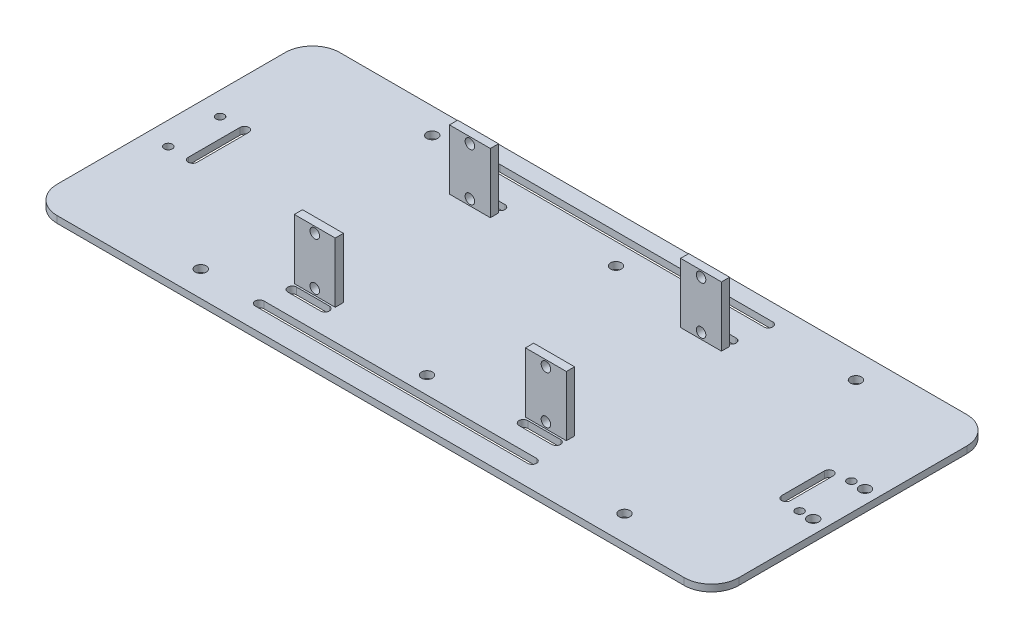
SolidWorks part; units mm, degrees
note: The reader was unsure of these and kept them because the rebuilt part matched: shared geometry of "草图1<3>".
ref_plane "前视基准面" through (0, 0, 0) normal (0, 0, 1) x (1, 0, 0)
ref_plane "上视基准面" through (0, 0, 0) normal (0, 1, 0) x (1, 0, 0)
ref_plane "右视基准面" through (0, 0, 0) normal (1, 0, 0) x (0, 0, -1)
other "Configuration Table"
sketch "草图1" plane through (0, 0, 0) normal (0, 1, 0) x (1, 0, 0)
  line L0 (3.7781, 0) -> (167.7978, 0) construction
  line L1 (0, 52.1835) -> (0, -52.1835) construction
  line L2 (115, -51.8188) -> (-115, -51.8188)
  line L3 (125, -41.8188) -> (125, 41.8188)
  line L4 (115, 51.8188) -> (-115, 51.8188)
  line L5 (-125, -41.8188) -> (-125, 41.8188)
  line L6 (125, -51.8188) -> (-125, 51.8188) construction
  line L7 (125, 51.8188) -> (-125, -51.8188) construction
  line L8 (-48.4, 32.2188) -> (-36.4, 32.2188) construction
  line L9 (-48.4, 33.8188) -> (-36.4, 33.8188)
  line L10 (-48.4, 30.6188) -> (-36.4, 30.6188)
  line L11 (-48.4, -32.2188) -> (-36.4, -32.2188) construction
  line L12 (-48.4, -33.8188) -> (-36.4, -33.8188)
  line L13 (-48.4, -30.6188) -> (-36.4, -30.6188)
  line L14 (48.4, -32.2188) -> (36.4, -32.2188) construction
  line L15 (48.4, -33.8188) -> (36.4, -33.8188)
  line L16 (48.4, -30.6188) -> (36.4, -30.6188)
  line L17 (48.4, 32.2188) -> (36.4, 32.2188) construction
  line L18 (48.4, 33.8188) -> (36.4, 33.8188)
  line L19 (48.4, 30.6188) -> (36.4, 30.6188)
  line L20 (108.4, 7.8731) -> (108.4, -7.8731) construction
  line L23 (-50, -42.6194) -> (50, -42.6194) construction
  line L24 (-98.458, 25) -> (-38.458, 25)
  line L25 (-98.458, 25) -> (-98.458, -25)
  line L26 (-98.458, -25) -> (-38.458, -25)
  line L27 (-38.458, 25) -> (-38.458, -25)
  line L28 (7.2728, 26.5) -> (90.2728, 26.5)
  line L29 (7.2728, 26.5) -> (7.2728, -26.5)
  line L30 (7.2728, -26.5) -> (90.2728, -26.5)
  line L31 (90.2728, 26.5) -> (90.2728, -26.5)
  line L32 (-35.1953, 23.2707) -> (1.4972, 23.2707)
  line L33 (-35.1953, 23.2707) -> (-35.1953, -23.2707)
  line L34 (-35.1953, -23.2707) -> (1.4972, -23.2707)
  line L35 (1.4972, 23.2707) -> (1.4972, -23.2707)
  line L40 (-50, -41.0194) -> (50, -41.0194)
  line L41 (-50, -44.2194) -> (50, -44.2194)
  line L42 (-107.902, 9.7565) -> (-107.902, -9.2435) construction
  line L45 (-50, 44.0491) -> (50, 44.0491) construction
  line L46 (-50, 42.4491) -> (50, 42.4491)
  line L47 (-50, 45.6491) -> (50, 45.6491)
  line L50 (110, 7.8731) -> (110, -7.8731)
  line L51 (106.8, 7.8731) -> (106.8, -7.8731)
  line L52 (-106.302, 9.7565) -> (-106.302, -9.2435)
  line L53 (-109.502, 9.7565) -> (-109.502, -9.2435)
  arc A0 (125, 41.8188) -> (115, 51.8188) centre (115, 41.8188) ccw
  arc A1 (115, -51.8188) -> (125, -41.8188) centre (115, -41.8188) ccw
  arc A2 (-115, -51.8188) -> (-125, -41.8188) centre (-115, -41.8188) cw
  arc A3 (-115, 51.8188) -> (-125, 41.8188) centre (-115, 41.8188) ccw
  circle A4 centre (120, 9.5) radius 2
  circle A5 centre (120, -9.5) radius 2
  arc A8 (-48.4, 33.8188) -> (-48.4, 30.6188) centre (-48.4, 32.2188) ccw
  arc A9 (-36.4, 30.6188) -> (-36.4, 33.8188) centre (-36.4, 32.2188) ccw
  arc A10 (-48.4, -33.8188) -> (-48.4, -30.6188) centre (-48.4, -32.2188) cw
  arc A11 (-36.4, -30.6188) -> (-36.4, -33.8188) centre (-36.4, -32.2188) cw
  arc A12 (48.4, -33.8188) -> (48.4, -30.6188) centre (48.4, -32.2188) ccw
  arc A13 (36.4, -30.6188) -> (36.4, -33.8188) centre (36.4, -32.2188) ccw
  arc A14 (48.4, 33.8188) -> (48.4, 30.6188) centre (48.4, 32.2188) cw
  arc A15 (36.4, 30.6188) -> (36.4, 33.8188) centre (36.4, 32.2188) cw
  arc A24 (-50, -41.0194) -> (-50, -44.2194) centre (-50, -42.6194) ccw
  arc A25 (50, -44.2194) -> (50, -41.0194) centre (50, -42.6194) ccw
  arc A28 (-50, 42.4491) -> (-50, 45.6491) centre (-50, 44.0491) cw
  arc A29 (50, 45.6491) -> (50, 42.4491) centre (50, 44.0491) cw
  arc A32 (110, 7.8731) -> (106.8, 7.8731) centre (108.4, 7.8731) ccw
  arc A33 (106.8, -7.8731) -> (110, -7.8731) centre (108.4, -7.8731) ccw
  circle A34 centre (115, 9.5) radius 1.5
  circle A35 centre (115, -9.5) radius 1.5
  circle A36 centre (-116.5676, 9.5) radius 1.5
  circle A37 centre (-116.5676, -9.5) radius 1.5
  arc A38 (-106.302, 9.7565) -> (-109.502, 9.7565) centre (-107.902, 9.7565) ccw
  arc A39 (-109.502, -9.2435) -> (-106.302, -9.2435) centre (-107.902, -9.2435) ccw
  circle A40 centre (-71.7179, 42.4491) radius 2
  circle A41 centre (3.4711, 34.6651) radius 2
  circle A42 centre (83.7149, 42.4491) radius 2
  circle A43 centre (83.7149, -42.4491) radius 2
  circle A44 centre (3.4711, -34.6651) radius 2
  circle A45 centre (-71.7179, -42.4491) radius 2
  point P1 (0, 0)
  point P32 (-42.4, 32.2188)
  point P39 (-42.4, -32.2188)
  point P46 (42.4, -32.2188)
  point P53 (42.4, 32.2188)
  point P60 (0, -42.6194)
  point P65 (-107.902, 0.2565)
  point P69 (-66.1502, 0)
  point P85 (108.4, 0)
  point P96 (-50, 32.2188)
  point P100 (0, 44.0491)
  point P116 (0, 0)
  dimension "D1" = 10
  dimension "D3" = 60
  dimension "D8" = 4
  dimension "D9" = 19
  dimension "D12" = 12
  dimension "D14" = 100
  dimension "D19" = 15
  dimension "D18" = 5
  dimension "D21" = 19
  dimension "D22" = 3
  dimension "D23" = 3
  dimension "D26" = 4
  dimension "D27" = 4
  dimension "D28" = 4
  dimension "D2" = 250
  dimension "D4" = 50
  dimension "D5" = 83
  dimension "D6" = 53
  dimension "D7" = 36.6924
  dimension "D10" = 3.2
  dimension "D11" = 18
  dimension "D13" = 75
  dimension "D15" = 3.2
  dimension "D16" = 19
  dimension "D17" = 5
  dimension "D20" = 3.2
  dimension "D24" = 19
  dimension "D25" = 3.2
extrude "凸台-拉伸1" add sketch "草图1" along normal mid plane 2.5 contours L4 A3 L5 A2 L2 A1 L3 A0 A44 A35 A34 A33 L51 A32 L50 A25 L41 A24 L40 A13 L16 A12 L15 A9 L10 A8 L9 L24 L27 L26 L25 L28 L31 L30 L29 L32 L35 L34 L33 A4 | L27 L24 L25 L26 | L35 L32 L33 L34 | L31 L28 L29 L30
extrude "凸台-拉伸2" add sketch "草图1<3>" along normal mid plane 2.5 contours L31 L28 L29 L30
sketch "草图1<3>" plane through (0, 0, 0) normal (0, 1, 0) x (1, 0, 0) same geometry as "草图1"
sketch "草图3" plane through (0, 1.25, 0) normal (0, 1, 0) x (1, 0, 0)
  line L0 (0, 0) -> (-129.9126, 0) construction
  line L1 (0, 0) -> (0, 63.0032) construction
  line L2 (-49.8914, -26.9486) -> (-34.8914, -26.9486)
  line L3 (-49.8914, 29.9486) -> (-34.8914, 29.9486)
  line L4 (-49.8914, 29.9486) -> (-49.8914, 26.9486)
  line L5 (-49.8914, 26.9486) -> (-34.8914, 26.9486)
  line L6 (-34.8914, 29.9486) -> (-34.8914, 26.9486)
  line L7 (-34.8914, -29.9486) -> (-34.8914, -26.9486)
  line L8 (-49.8914, -29.9486) -> (-34.8914, -29.9486)
  line L9 (-49.8914, -29.9486) -> (-49.8914, -26.9486)
  line L10 (49.8914, -29.9486) -> (49.8914, -26.9486)
  line L11 (49.8914, -29.9486) -> (34.8914, -29.9486)
  line L12 (34.8914, -29.9486) -> (34.8914, -26.9486)
  line L13 (49.8914, -26.9486) -> (34.8914, -26.9486)
  line L14 (49.8914, 26.9486) -> (34.8914, 26.9486)
  line L15 (34.8914, 29.9486) -> (34.8914, 26.9486)
  line L16 (49.8914, 29.9486) -> (34.8914, 29.9486)
  line L17 (49.8914, 29.9486) -> (49.8914, 26.9486)
  dimension "D1" = 15
  dimension "D2" = 3
extrude "凸台-拉伸3" add sketch "草图3" along normal blind 22
sketch "草图4" plane through (0, 0, 29.9486) normal (0, 0, 1) x (1, 0, 0)
  line L0 (-49.8914, 23.25) -> (-34.8914, 23.25) construction
  line L1 (-49.8914, 23.25) -> (-49.8914, 1.25) construction
  line L2 (115, 1.25) -> (-115, 1.25) construction
  circle A0 centre (-42.3914, 21) radius 1.75
  circle A1 centre (-42.3914, 3.5) radius 1.75
  dimension "D3" = 3.5
  dimension "D6" = 3.5
  dimension "D1" = 2.25
  dimension "D2" = 7.5
  dimension "D4" = 7.5
  dimension "D5" = 2.25
extrude "切除-拉伸1" cut sketch "草图4" against normal through all
mirror "镜向1" about plane through (0, 0, 0) normal (1, 0, 0) of "切除-拉伸1"
